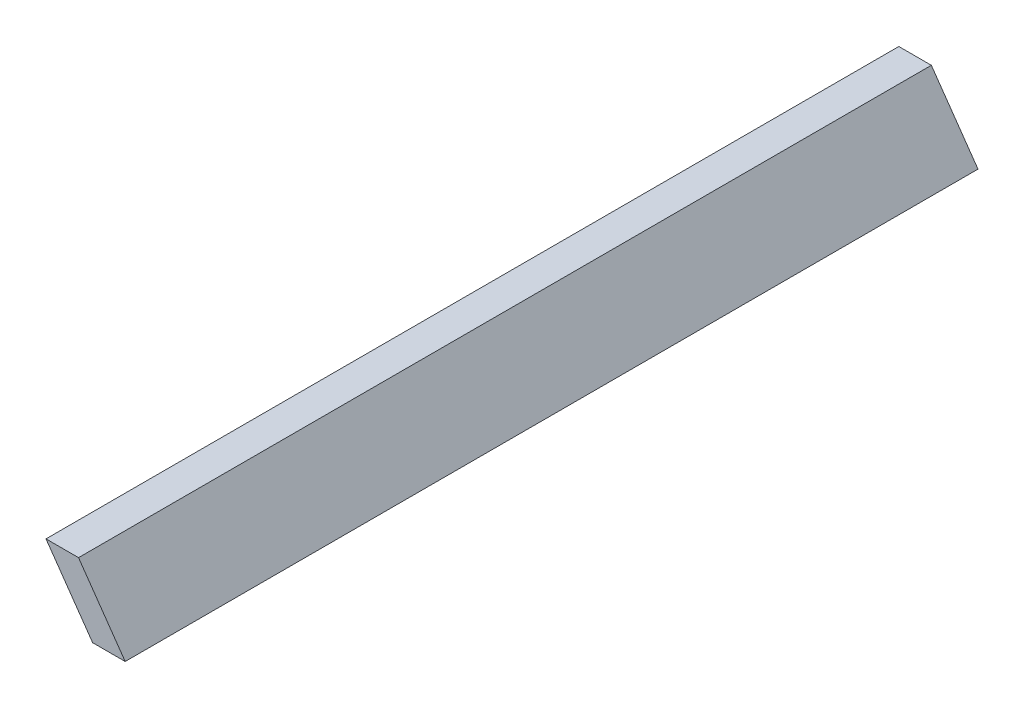
SolidWorks part; units mm, degrees
material "Gray Cast Iron"
ref_plane "Front Plane" through (0, 0, 0) normal (0, 0, 1) x (1, 0, 0)
ref_plane "Top Plane" through (0, 0, 0) normal (0, 1, 0) x (1, 0, 0)
ref_plane "Right Plane" through (0, 0, 0) normal (1, 0, 0) x (0, 0, -1)
sketch "Sketch6" plane through (0, 0, 0) normal (0, 0, 1) x (1, 0, 0)
  line B0 (-34.7427, -15.875) -> (92.2573, -15.875)
  line B1 (92.2573, 0) -> (65.2665, 0)
  line B2 (-11.1158, 15.875) -> (0, 0)
  line B3 (0, 0) -> (-34.7427, 0)
  line B4 (-7.7519, 0) -> (-18.8677, 15.875)
  line B5 (-18.8677, 15.875) -> (-11.1158, 15.875)
  line B6 (12.701, 15.875) -> (12.701, -3.175)
  line B7 (12.701, -3.175) -> (44.8136, -3.175)
  line B8 (12.701, 15.875) -> (-11.1158, 15.875)
  line B9 (-34.7427, 0) -> (-34.7427, 31.75)
  line B10 (-34.7427, 31.75) -> (92.2573, 31.75)
  line B11 (92.2573, 31.75) -> (92.2573, 0)
  line B12 (28.7573, 31.75) -> (28.7573, -15.875) construction
  line B13 (-7.7519, 0) -> (65.2665, 0) construction
  line B14 (0.0553, 21.082) -> (57.4593, 21.082) construction
  line B15 (3.3573, -8.001) -> (54.1573, -8.001) construction
  line B16 (3.3573, -8.001) -> (3.3573, 7.9375) construction
  line B17 (54.1573, -8.001) -> (54.1573, 7.9375) construction
  line B18 (-24.0747, 7.9375) -> (81.5893, 7.9375) construction
  circle B19 centre (28.7573, 6.35) radius 18.669 construction
sketch_block_instance "dovetail pair-1"
sketch_block "dovetail pair" parameters "D8"=37.338, "D1"=55, "D2"=127, "D3"=6.35, "D4"=15.875, "D5"=31.75, "D6"=95.25, "D7"=19.05, "D9"=55, "D10"=31.75, "D11"=50.8, "D12"=23.876, "D13"=7.874, "D14"=10.668, "D15"=34.798, "D16"=21.082, "D17"=7.9375
sketch "end-profile" plane through (0, 0, 0) normal (0, 0, 1) x (1, 0, 0)
  line L0 (0, 0) -> (-7.7519, 0)
  line L4 (-11.1158, 15.875) -> (0, 0) construction
  line L5 (-18.8677, 15.875) -> (-11.1158, 15.875) construction
  line L6 (-7.7519, 0) -> (-18.8677, 15.875) construction
  line L7 (-11.1158, 15.875) -> (0, 0)
  line L8 (-18.8677, 15.875) -> (-11.1158, 15.875)
  line L9 (-7.7519, 0) -> (-18.8677, 15.875)
extrude "Boss-Extrude1" add sketch "end-profile" along normal blind 203.2
ref_plane "screw pocket Plane1" through (-18.8677, 0, 0) normal (1, 0, 0) x (0, 0, -1)
sketch "Sketch4" plane through (-18.8677, 0, 0) normal (1, 0, 0) x (0, 0, -1)
  line L0 (0, 7.9375) -> (-201.1082, 7.9375) construction
  line L3 (-180.1412, 7.9375) -> (-180.1412, 0)
  line L4 (-180.1412, 0) -> (-173.367, 0)
  line L5 (-173.367, 0) -> (-173.367, 7.9375)
  line L6 (-142.0412, 7.9375) -> (-142.0412, 0)
  line L7 (-142.0412, 0) -> (-135.267, 0)
  line L8 (-135.267, 0) -> (-135.267, 7.9375)
  line L9 (-103.9412, 7.9375) -> (-103.9412, 0)
  line L10 (-103.9412, 0) -> (-97.167, 0)
  line L11 (-97.167, 0) -> (-97.167, 7.9375)
  line L12 (-65.8412, 7.9375) -> (-65.8412, 0)
  line L13 (-65.8412, 0) -> (-59.067, 0)
  line L14 (-59.067, 0) -> (-59.067, 7.9375)
  line L15 (-27.7412, 7.9375) -> (-27.7412, 0)
  line L16 (-27.7412, 0) -> (-20.967, 0)
  line L17 (-20.967, 0) -> (-20.967, 7.9375)
  line L18 (-180.1412, 7.9375) -> (-142.0412, 7.9375) construction
  line L19 (-203.2, 0) -> (0, 0) construction
  line L21 (0, 0) -> (0, 15.875) construction
  arc A0 (-173.367, 7.9375) -> (-180.1412, 7.9375) centre (-176.7541, 7.9375) ccw
  arc A1 (-135.267, 7.9375) -> (-142.0412, 7.9375) centre (-138.6541, 7.9375) ccw
  arc A2 (-97.167, 7.9375) -> (-103.9412, 7.9375) centre (-100.5541, 7.9375) ccw
  arc A3 (-59.067, 7.9375) -> (-65.8412, 7.9375) centre (-62.4541, 7.9375) ccw
  arc A4 (-20.967, 7.9375) -> (-27.7412, 7.9375) centre (-24.3541, 7.9375) ccw
  dimension "D1" = 6.7742
  dimension "D2" = 38.1
  dimension "D3" = 5
extrude "Cut-Extrude1" cut sketch "Sketch4" along normal blind 7.112
sketch "Sketch5" [suppressed] plane through (-18.8677, 0, 0) normal (1, 0, 0) x (0, 0, -1)
  line L0 (0, 7.9375) -> (-127, 7.9375) construction
  line L3 (-104.9871, 7.9375) -> (-104.9871, 0)
  line L5 (-104.9871, 0) -> (-98.2129, 0)
  line L6 (-98.2129, 0) -> (-98.2129, 7.9375)
  line L7 (-66.8871, 7.9375) -> (-66.8871, 0)
  line L8 (-66.8871, 0) -> (-60.1129, 0)
  line L9 (-60.1129, 0) -> (-60.1129, 7.9375)
  line L10 (-28.7871, 7.9375) -> (-28.7871, 0)
  line L11 (-28.7871, 0) -> (-22.0129, 0)
  line L12 (-22.0129, 0) -> (-22.0129, 7.9375)
  line L13 (-104.9871, 7.9375) -> (-66.8871, 7.9375) construction
  line L14 (-127, 0) -> (-127, 15.875) construction
  line L15 (-127, 0) -> (0, 0) construction
  line L16 (0, 0) -> (0, 15.875) construction
  arc A0 (-98.2129, 7.9375) -> (-104.9871, 7.9375) centre (-101.6, 7.9375) ccw
  arc A1 (-60.1129, 7.9375) -> (-66.8871, 7.9375) centre (-63.5, 7.9375) ccw
  arc A2 (-22.0129, 7.9375) -> (-28.7871, 7.9375) centre (-25.4, 7.9375) ccw
  dimension "D1" = 6.7742
  dimension "D2" = 38.1
extrude "Cut-Extrude2" [suppressed] cut sketch "Sketch5" along normal blind 7.112
equation "\"dovetail-angle\" = 55"
equation "\"dovetail-stock-width\" = 5"
equation "\"dovetail-stock-height\" = 1.25"
equation "\"dovetail-depth\" = 0.5 * \"dovetail-stock-height\""
equation "\"dovetail-throat-width\" = \"dovetail-stock-width\" - (2 * \"dovetail-depth\")"
equation "\"delta-x\" = 6"
equation "\"delta-y\" = 3"
equation "\"delta-z\"= 2.5"
equation "\"acme-nut-height\"= 0.5"
equation "\"acme-nut-width\"= 0.75"
equation "\"gib-thickness\" = 0.25"
equation "\"x-slide-length\" = \"dovetail-stock-width\" + \"delta-x\""
equation "\"y-slide-length\" = \"dovetail-stock-width\" + \"delta-y\""
equation "\"dog-point-diam\" = .149"
equation "\"dog-point-length\" = .067"
equation "\"dovetail-double-height\" = 2 * \"dovetail-depth\" + 0.5"
equation "\"acme-major-diam\" = .5"
equation "\"acme-pitch-diam\" = 0.45"
equation "\"acme-minor-diam\" = 0.4"
equation "\"acme-nut-od\" = 1.47"
equation "\"acme-nut-length\" = 1"
equation "\"acme-nut-trim-height\" = .75"
equation "\"screw-bearing-od\" = 0.5"
equation "\"screw-bearing-length\" = .375"
equation "\"screw-bearing-id\" = .375"
equation "\"end-plate-thickness\" = \"screw-bearing-length\""
equation "\"screw-add-length\" = 2 * \"end-plate-thickness\" + 1 + 0.5"
equation "\"x-screw-length\" = \"x-slide-length\" + \"screw-add-length\""
equation "\"y-screw-length\" = \"y-slide-length\" + \"screw-add-length\""
equation "\"acme-nut-mount-hole-space-horz\" = 0.95"
equation "\"acme-nut-mount-hole-space-vert\" = 0.5 * \"acme-nut-length\""
equation "\"vise-hole-center-dist\" = 6.75"
equation "\"wiper_plate_clearance\" = .03"
equation "\"dial-width\" = 0.5"
equation "\"quarter-twenty-free-fit\" = .2667"
equation "\"D1@Sketch4\"=\"quarter-twenty-free-fit\""
equation "\"D1@Sketch5\"=\"quarter-twenty-free-fit\""
equation "\"D2@dovetail pair\"=\"dovetail-stock-width\""
equation "\"D1@dovetail pair\"=\"dovetail-angle\""
equation "\"D3@dovetail pair\"=\"gib-thickness\""
equation "\"D4@dovetail pair\"=\"dovetail-depth\""
equation "\"D5@dovetail pair\"=\"dovetail-stock-height\""
equation "\"D6@dovetail pair\"=\"dovetail-throat-width\""
equation "\"D10@dovetail pair\"=\"dovetail-stock-height\""
equation "\"D7@dovetail pair\"=\"acme-nut-trim-height\""
equation "\"D8@dovetail pair\"=\"acme-nut-od\""
equation "\"D9@dovetail pair\"=\"dovetail-angle\""
equation "\"D17@dovetail pair\"=\"dovetail-depth\"/2"
equation "\"acme-nut-trim-width\" = 1.25"
equation "\"acme_nut_clearance\" = .01"
equation "\"dovetail_male_clearance\" = .01"
